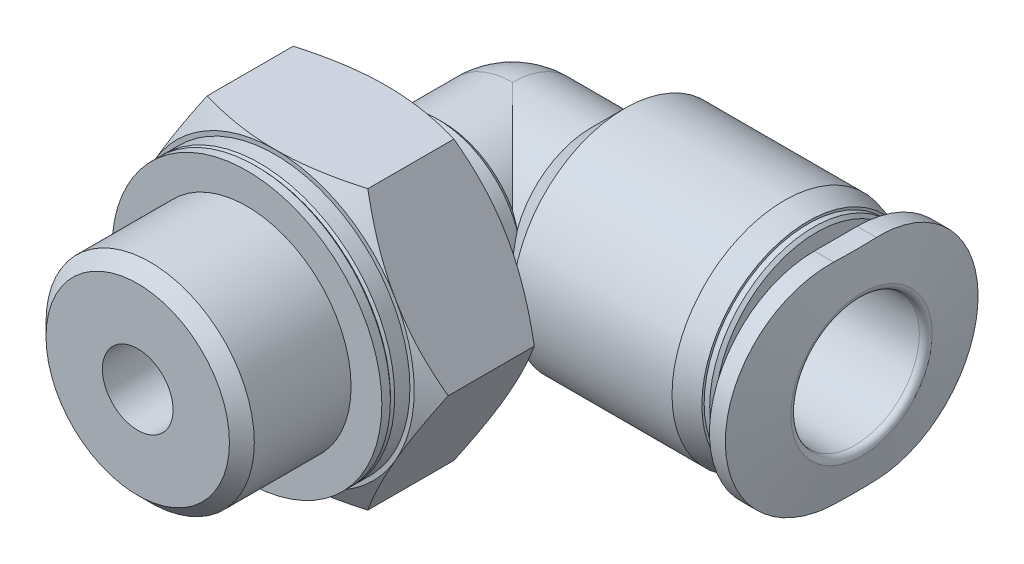
SolidWorks part; units mm, degrees
ref_plane "Front Plane" through (0, 0, 0) normal (0, 0, 1) x (1, 0, 0)
ref_plane "Top Plane" through (0, 0, 0) normal (0, 1, 0) x (1, 0, 0)
ref_plane "Right Plane" through (0, 0, 0) normal (1, 0, 0) x (0, 0, -1)
sketch "Sketch1" plane through (0, 0, 0) normal (0, 0, 1) x (1, 0, 0)
  line L0 (0, 3.675) -> (3.675, 3.675)
  line L1 (3.675, 3.675) -> (5.25, 5.25)
  line L2 (5.25, 5.25) -> (12.7, 5.25)
  line L3 (12.7, 5.25) -> (13.8, 4.9553)
  line L4 (13.8, 4.9553) -> (13.8, 4.8481)
  line L5 (13.8, 4.8481) -> (14.0586, 4.8481)
  line L6 (14.0586, 4.8481) -> (14.2, 4.7067)
  line L7 (14.2, 4.7067) -> (14.2, 3.5)
  line L8 (14.2, 3.5) -> (14.73, 3.5)
  line L9 (15.1, 3.87) -> (15.1, 6.9)
  line L10 (15.1, 6.9) -> (15.4974, 6.9)
  line L11 (15.6944, 6.7347) -> (16.3, 3.3)
  line L12 (16.3, 3.3) -> (16.3, 0)
  line L13 (16.3, 0) -> (-3.675, 0)
  line L14 (16.3, 0) -> (-3.675, 0) construction
  arc A0 (-3.675, 0) -> (0, 3.675) centre (0, 0) cw
  arc A1 (14.73, 3.5) -> (15.1, 3.87) centre (14.73, 3.87) ccw
  arc A2 (15.4974, 6.9) -> (15.6944, 6.7347) centre (15.4974, 6.7) cw
revolve "Revolve1" add sketch "Sketch1" angle 360 about L14
sketch "Sketch2" plane through (0, 0, 0) normal (1, 0, 0) x (0, 0, -1)
  line L0 (-12.4, 0) -> (-12.4, 6.3)
  line L1 (-12.4, 6.3) -> (-12, 6.3)
  line L2 (-12, 6.3) -> (-11.9, 6.2)
  line L3 (-11.9, 6.2) -> (-11.8, 6.3)
  line L4 (-11.8, 6.3) -> (-11.0875, 6.3)
  line L5 (-11.0875, 6.3) -> (-11.0875, 6.5)
  line L6 (-11.0875, 6.5) -> (-10.4871, 7.54)
  line L7 (-10.4871, 7.54) -> (-6.5067, 7.54)
  line L8 (-6.5067, 7.54) -> (-5.9062, 6.5)
  line L9 (-5.9062, 6.5) -> (-5.9062, 3.9375)
  line L10 (-5.9062, 3.9375) -> (-3.5, 3.9375)
  line L11 (-3.5, 3.9375) -> (-3.2375, 3.675)
  line L12 (-3.2375, 3.675) -> (0, 3.675)
  line L13 (0, 3.675) -> (0, 0)
  line L14 (0, 0) -> (-12.4, 0)
  line L15 (0, 0) -> (-12.4, 0) construction
revolve "Revolve2" add sketch "Sketch2" angle 360 about L15
sketch "Sketch3" plane through (0, 0, 0) normal (1, 0, 0) x (0, 0, -1)
  line L0 (-17.5, 0) -> (-17.5, 4.283)
  line L1 (-17.5, 4.283) -> (-16.919, 4.864)
  line L2 (-16.919, 4.864) -> (-12.4, 4.864)
  line L3 (-12.4, 4.864) -> (-12.4, 0)
  line L4 (-12.4, 0) -> (-17.5, 0)
  line L5 (-12.4, 0) -> (-17.5, 0) construction
revolve "Revolve3" add sketch "Sketch3" angle 360 about L5
cosmetic thread "Cosmetic Thread1" parameters "D1"=5.1, "D2"=8.566
ref_plane "Plane1" through (16.3, 0, 0) normal (1, 0, 0) x (0, 0, -1)
sketch "Sketch4" plane through (16.3, 0, 0) normal (1, 0, 0) x (0, 0, -1)
  line L0 (-11.8, -6.8127) -> (0, -13.6255)
  line L1 (0, -13.6255) -> (11.8, -6.8127)
  line L2 (11.8, -6.8127) -> (11.8, 6.8127)
  line L3 (11.8, 6.8127) -> (0, 13.6255)
  line L4 (0, 13.6255) -> (-11.8, 6.8127)
  line L5 (-11.8, 6.8127) -> (-11.8, -6.8127)
  line L6 (-1, -4.9) -> (1, -4.9)
  line L7 (1, 4.9) -> (-1, 4.9)
  arc A0 (-1, 4.9) -> (-1, -4.9) centre (-1, 0) ccw
  arc A1 (1, -4.9) -> (1, 4.9) centre (1, 0) ccw
extrude "Cut-Extrude1" cut sketch "Sketch4" against normal blind 1.2
sketch "Sketch5" plane through (0, 0, 0) normal (0, 1, 0) x (1, 0, 0)
  line L0 (0, 1.65) -> (4.4, 1.65)
  line L1 (4.4, 1.65) -> (4.4, 3)
  line L2 (4.4, 3) -> (16, 3)
  line L3 (16.3, 3.3) -> (16.3, 0)
  line L4 (16.3, 0) -> (-1.65, 0)
  line L5 (16.3, 0) -> (-1.65, 0) construction
  arc A0 (-1.65, 0) -> (0, 1.65) centre (0, 0) cw
  arc A1 (16, 3) -> (16.3, 3.3) centre (16, 3.3) ccw
sketch "Sketch6" plane through (0, 0, 0) normal (1, 0, 0) x (0, 0, -1)
  line L0 (-17.5, 0) -> (-17.5, 1.65)
  line L1 (-17.5, 1.65) -> (0, 1.65)
  line L2 (0, 1.65) -> (0, 0)
  line L3 (0, 0) -> (-17.5, 0)
  line L4 (0, 0) -> (-17.5, 0) construction
revolve "Cut-Revolve1" cut sketch "Sketch6" angle 360 about L4
revolve "Cut-Revolve2" cut sketch "Sketch5" angle 360 about L5
ref_plane "Plane2" through (0, 0, 12.4) normal (0, 0, 1) x (1, 0, 0)
sketch "Sketch7" plane through (0, 0, 12.4) normal (0, 0, 1) x (1, 0, 0)
  line L0 (-13, -13) -> (13, -13)
  line L1 (13, -13) -> (13, 13)
  line L2 (13, 13) -> (-13, 13)
  line L3 (-13, 13) -> (-13, -13)
  line L4 (-7.5056, 0) -> (-3.7528, -6.5)
  line L5 (-3.7528, -6.5) -> (3.7528, -6.5)
  line L6 (3.7528, -6.5) -> (7.5056, 0)
  line L7 (7.5056, 0) -> (3.7528, 6.5)
  line L8 (3.7528, 6.5) -> (-3.7528, 6.5)
  line L9 (-3.7528, 6.5) -> (-7.5056, 0)
extrude "Cut-Extrude2" cut sketch "Sketch7" against normal blind 6.5667
ref_plane "Plane3" through (0, 0, 12.4) normal (0, 0, 1) x (1, 0, 0)
ref_plane "Plane4" through (4.4, 0, 0) normal (1, 0, 0) x (0, 0, -1)
ref_plane "ANBAU XY" through (0, 0, 12.4) normal (0, 0, 1) x (1, 0, 0)
ref_plane "ANBAU XZ" through (0, 0, 0) normal (0, -1, 0) x (-1, 0, 0)
ref_plane "ANBAU YZ" through (0, 0, 0) normal (1, 0, 0) x (0, 0, -1)
ref_axis "ANBAU X" through (-80.9, 0, 12.4) along (1, 0, 0)
ref_axis "ANBAU Y" through (0, -50, 12.4) along (0, 1, 0)
ref_axis "ANBAU Z" through (0, 0, 80.9) along (0, 0, -1)
sketch3d "ANBAU"
  point P0 (0, 0, 12.4)
ref_plane "ANBAU_STD XY" through (0, 0, 12.4) normal (0, 0, -1) x (-1, 0, 0)
ref_plane "ANBAU_STD XZ" through (0, 0, 0) normal (0, 1, 0) x (1, 0, 0)
ref_plane "ANBAU_STD YZ" through (0, 0, 0) normal (1, 0, 0) x (0, 0, -1)
ref_axis "ANBAU_STD X" through (-80.9, 0, 12.4) along (1, 0, 0)
ref_axis "ANBAU_STD Y" through (0, 50, 12.4) along (0, -1, 0)
ref_axis "ANBAU_STD Z" through (0, 0, -80.9) along (0, 0, 1)
sketch3d "ANBAU_STD"
  point P0 (0, 0, 12.4)
ref_plane "CPV XY" through (0, 0, 12.4) normal (0, 0, -1) x (-1, 0, 0)
ref_plane "CPV XZ" through (0, 0, 0) normal (0, 1, 0) x (1, 0, 0)
ref_plane "CPV YZ" through (0, 0, 0) normal (1, 0, 0) x (0, 0, -1)
ref_axis "CPV X" through (-80.9, 0, 12.4) along (1, 0, 0)
ref_axis "CPV Y" through (0, 50, 12.4) along (0, -1, 0)
ref_axis "CPV Z" through (0, 0, -80.9) along (0, 0, 1)
sketch3d "CPV"
  point P0 (0, 0, 12.4)
ref_plane "FDT_MOUNT XY" through (0, 0, 12.4) normal (0, 0, 1) x (1, 0, 0)
ref_plane "FDT_MOUNT XZ" through (0, 0, 0) normal (1, 0, 0) x (0, 0, -1)
ref_plane "FDT_MOUNT YZ" through (0, 0, 0) normal (0, 1, 0) x (1, 0, 0)
ref_axis "FDT_MOUNT X" through (0, -50, 12.4) along (0, 1, 0)
ref_axis "FDT_MOUNT Y" through (80.9, 0, 12.4) along (-1, 0, 0)
ref_axis "FDT_MOUNT Z" through (0, 0, 50) along (0, 0, -1)
sketch3d "FDT_MOUNT"
  point P0 (0, 0, 12.4)
ref_plane "FDT_SCHLAUCH XY" through (4.4, 0, 0) normal (1, 0, 0) x (0, 0, -1)
ref_plane "FDT_SCHLAUCH XZ" through (0, 0, 0) normal (0, -1, 0) x (-1, 0, 0)
ref_plane "FDT_SCHLAUCH YZ" through (0, 0, 0) normal (0, 0, -1) x (-1, 0, 0)
ref_axis "FDT_SCHLAUCH X" through (4.4, 0, 80.9) along (0, 0, -1)
ref_axis "FDT_SCHLAUCH Y" through (4.4, -50, 0) along (0, 1, 0)
ref_axis "FDT_SCHLAUCH Z" through (80.9, 0, 0) along (-1, 0, 0)
sketch3d "FDT_SCHLAUCH"
  point P0 (4.4, 0, 0)
